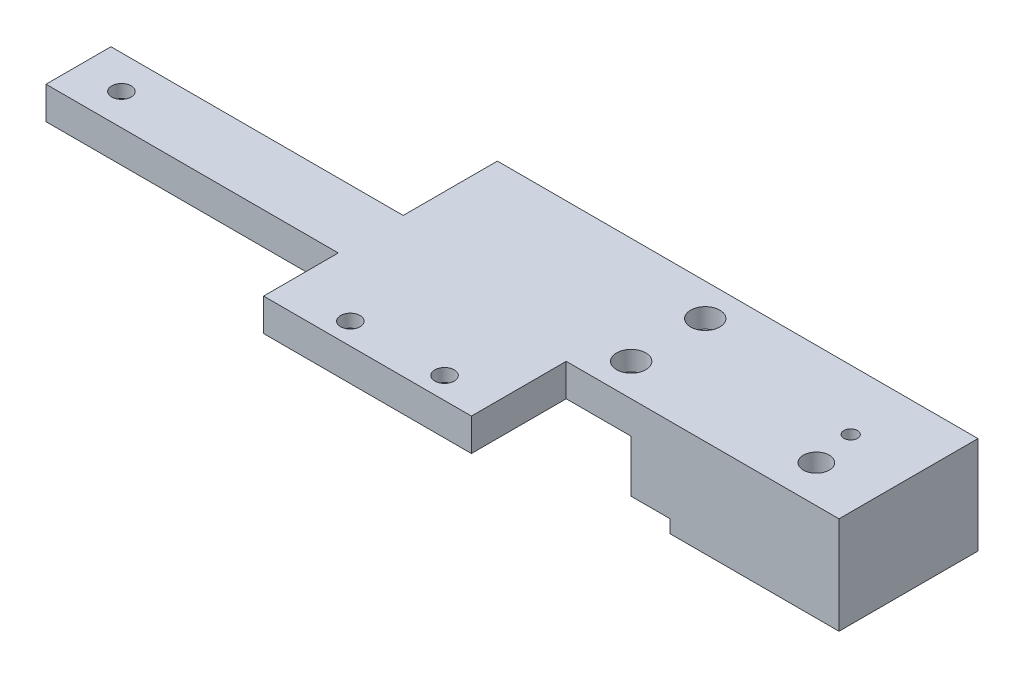
SolidWorks part; units mm, degrees
ref_plane "前视基准面" through (0, 0, 0) normal (0, 0, 1) x (1, 0, 0)
ref_plane "上视基准面" through (0, 0, 0) normal (0, 1, 0) x (1, 0, 0)
ref_plane "右视基准面" through (0, 0, 0) normal (1, 0, 0) x (0, 0, -1)
other "Configuration Table"
sketch "草图1" plane through (0, 0, 0) normal (0, 1, 0) x (1, 0, 0)
  line L33 (0, -21.4) -> (42, -21.4)
  line L34 (0, -21.4) -> (0, 0)
  line L35 (0, 0) -> (42, 0)
  line L36 (42, -21.4) -> (42, 0)
  point P0 (-90.6464, 22.0667)
  dimension "D3" = 21.4
  dimension "D6" = 42
extrude "凸台-拉伸1" add sketch "草图1" along normal blind 12 contours L33 L36 L35 L34 | L33 | L34 region at (21, 0, 10.7)
sketch "草图2" plane through (0, 0, 0) normal (0, 0, -1) x (-1, 0, 0)
  line L0 (0, 12) -> (-42, 12) construction
  line L1 (0, 0) -> (-10, 0)
  line L2 (0, 0) -> (0, 10)
  line L3 (0, 10) -> (-10, 10)
  line L4 (-10, 0) -> (-10, 10)
  line L6 (-10, 0) -> (-16, 0)
  line L7 (-10, 0) -> (-10, 2)
  line L8 (-10, 2) -> (-16, 2)
  line L9 (-16, 0) -> (-16, 2)
  dimension "D1" = 2
  dimension "D2" = 10
  dimension "D3" = 2
  dimension "D4" = 6
extrude "切除-拉伸1" cut sketch "草图2" against normal through all contours L7 L8 L9 L6 | L4 L3 L2 L1
sketch "草图3" plane through (0, 0, 0) normal (0, -1, 0) x (1, 0, 0)
  circle A0 centre (20.3, 7.4) radius 5
  circle A1 centre (31.6497, 9.2532) radius 1.05
  circle A4 centre (31.6497, 9.2532) radius 8.5
  circle A6 centre (32.7692, 15.656) radius 5
  circle A7 centre (31.6497, 9.2532) radius 3.5
  circle A8 centre (20.3, 7.4) radius 3.1
  circle A10 centre (32.7692, 15.656) radius 3.1
  circle A11 centre (32.7692, 15.656) radius 2
  dimension "D1" = 10
  dimension "D2" = 17
  dimension "D3" = 7
  dimension "D4" = 10
  dimension "D5" = 6.2
  dimension "D6" = 4
  dimension "D7" = 6.2
  dimension "D8" = 2.1
extrude "切除-拉伸2" cut sketch "草图3" against normal blind 5.5 contours A0
extrude "切除-拉伸3" cut sketch "草图3<3>" against normal blind 3 contours A4
sketch "草图3<3>" plane through (0, 0, 0) normal (0, -1, 0) x (1, 0, 0) same geometry as "草图3"
extrude "切除-拉伸4" cut sketch "草图3<4>" against normal blind 7 contours A7
sketch "草图3<4>" plane through (0, 0, 0) normal (0, -1, 0) x (1, 0, 0) same geometry as "草图3"
extrude "切除-拉伸5" cut sketch "草图3<5>" against normal blind 8.5 contours A6
sketch "草图3<5>" plane through (0, 0, 0) normal (0, -1, 0) x (1, 0, 0) same geometry as "草图3"
extrude "切除-拉伸6" cut sketch "草图3<6>" against normal blind 2.6 from surface contours A10 starting at face at (32.7692, 8.5, 10.656)
sketch "草图3<6>" plane through (0, 0, 0) normal (0, -1, 0) x (1, 0, 0) same geometry as "草图3"
extrude "切除-拉伸7" cut sketch "草图3<7>" against normal blind 2.6 from surface contours A8 starting at face at (20.3, 5.5, 2.4)
sketch "草图3<7>" plane through (0, 0, 0) normal (0, -1, 0) x (1, 0, 0) same geometry as "草图3"
sketch "草图4" plane through (0, 12, 0) normal (0, 1, 0) x (1, 0, 0)
  line L1 (42, 0) -> (-32, 0)
  line L2 (42, 0) -> (42, -36)
  line L3 (42, -36) -> (-32, -36)
  line L4 (-32, 0) -> (-32, -36)
  line L5 (0, -21.4) -> (0, 0) construction
  line L10 (-32, -14.5) -> (-77, -14.5)
  line L11 (-32, -14.5) -> (-32, -24.5)
  line L12 (-32, -24.5) -> (-77, -24.5)
  line L13 (-77, -14.5) -> (-77, -24.5)
  line L14 (42, -21.4) -> (0, -21.4)
  line L15 (42, -21.4) -> (42, -36)
  line L16 (42, -36) -> (0, -36)
  line L17 (0, -21.4) -> (0, -36)
  line M5 (0, -21.4) -> (42, -21.4)
  line M6 (42, -21.4) -> (42, 0)
  line M7 (42, 0) -> (0, 0)
  line M8 (0, 0) -> (0, -21.4)
  dimension "D1" = 36
  dimension "D2" = 74
  dimension "D3" = 45
  dimension "D4" = 10
  dimension "D5" = 14.5
extrude "凸台-拉伸2" add sketch "草图4" along normal blind 5 from surface contours M8 M5 M6 M7 | L17 L1 L4 L3 M8 | L10 L13 L12 L4 region at (21, 12, 10.7) region at (-16, 12, 18) region at (-54.5, 12, 19.5) starting at face at (5, 10, 10.7)
sketch "草图5" plane through (0, 10, 0) normal (0, -1, 0) x (1, 0, 0)
  circle A0 centre (-70.2308, 19.656) radius 1.5
  circle A1 centre (-21.9808, 32.656) radius 1.5
  circle A2 centre (-7.4808, 32.656) radius 1.5
  circle A3 centre (-7.4808, 32.656) radius 2.25
  circle A4 centre (-21.9808, 32.656) radius 2.25
  circle A5 centre (-70.2308, 19.656) radius 2.25
  dimension "D1" = 3
  dimension "D2" = 4.5
extrude "切除-拉伸8" cut sketch "草图5" against normal offset from surface (3 mm away) 2 contours A5 | A4 | A3 up to face at (-19.8, 15, 19.28)
extrude "切除-拉伸9" cut sketch "草图5<3>" against normal through all contours A0 | A1 | A2
sketch "草图5<3>" plane through (0, 10, 0) normal (0, -1, 0) x (1, 0, 0) same geometry as "草图5"
extrude "切除-拉伸10" cut sketch "草图3<8>" against normal through all contours A11 | A1
sketch "草图3<8>" plane through (0, 0, 0) normal (0, -1, 0) x (1, 0, 0) same geometry as "草图3"
sketch "草图6" plane through (0, 15, 0) normal (0, 1, 0) x (1, 0, 0)
  circle A0 centre (5, -5) radius 2.25
  circle A1 centre (5, -16.4) radius 2.25
  circle A2 centre (5, -5) radius 1.5
  circle A3 centre (5, -16.4) radius 1.5
  dimension "D1" = 3
  dimension "D2" = 4.5
extrude "切除-拉伸11" cut sketch "草图6" against normal through all contours A2 | A3
extrude "切除-拉伸12" cut sketch "草图6<3>" against normal offset from surface (3 mm away) 2 contours A1 | A0 up to face at (3.5, 10, 5)
sketch "草图6<3>" plane through (0, 15, 0) normal (0, 1, 0) x (1, 0, 0) same geometry as "草图6"
sketch "草图7" plane through (0, 0, 0) normal (0, -1, 0) x (1, 0, 0)
  line L0 (16, 21.4) -> (42, 21.4) construction
  line L1 (42, 21.4) -> (42, 0) construction
  line L2 (16, 0) -> (42, 0) construction
  circle A0 centre (39.5, 18.4) radius 0.8
  circle A1 centre (39.5, 2.5) radius 0.8
  dimension "D1" = 1.6
  dimension "D2" = 3
  dimension "D3" = 2.5
  dimension "D4" = 2.5
  dimension "D5" = 2.5
extrude "切除-拉伸13" cut sketch "草图7" against normal blind 4 contours A1 | A0
extrude "切除-拉伸14" cut sketch "草图3<9>" against normal blind 2.6 from surface contours A10 starting at face at (32.7692, 8.5, 12.556)
sketch "草图3<9>" plane through (0, 0, 0) normal (0, -1, 0) x (1, 0, 0) same geometry as "草图3"
